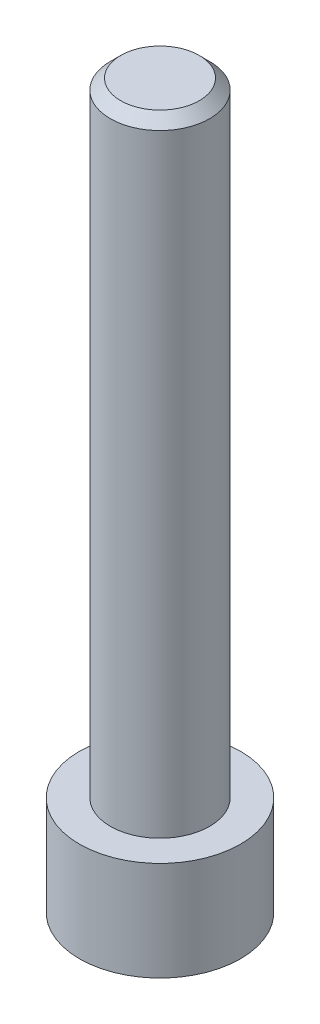
SolidWorks part; units mm, degrees
ref_plane "Front Plane" through (0, 0, 0) normal (0, 0, 1) x (1, 0, 0)
ref_plane "Top Plane" through (0, 0, 0) normal (0, 1, 0) x (1, 0, 0)
ref_plane "Right Plane" through (0, 0, 0) normal (1, 0, 0) x (0, 0, -1)
sketch "Sketch1" plane through (0, 0, 0) normal (0, 1, 0) x (1, 0, 0)
  line L1 (4.4745, 0) -> (2.2372, 3.875) construction
  line L2 (2.2372, 3.875) -> (-2.2372, 3.875) construction
  line L3 (-2.2372, 3.875) -> (-4.4745, 0) construction
  line L4 (-4.4745, 0) -> (-2.2372, -3.875) construction
  line L5 (-2.2372, -3.875) -> (2.2372, -3.875) construction
  line L6 (2.2372, -3.875) -> (4.4745, 0) construction
  circle A0 centre (0, 0) radius 3.875
  dimension "D1" = 7.75
extrude "Boss-Extrude1" add sketch "Sketch1" along normal blind 34.78
sketch "Sketch2" plane through (0, 34.78, 0) normal (0, 1, 0) x (1, 0, 0)
  circle A0 centre (0, 0) radius 2.39
  dimension "D1" = 4.78
extrude "Cut-Extrude1" cut sketch "Sketch2" against normal blind 30 flip side to cut
ref_axis "Axis1" through (0, 4.78, 0) along (0, 1, 0)
chamfer "Chamfer1" distance 0.5 angle 45 1 edges at (0, 34.78, 2.39)
sketch "Sketch5" plane through (0, 34.78, 0) normal (0, 1, 0) x (1, 0, 0)
  circle A0 centre (0, 0) radius 2.39
  dimension "D1" = 4.78
curve "Helix/Spiral1" pitch 0.7 height 25 turns 35.7143
ref_plane "Plane1" through (0, 34.78, 2.39) normal (-0.9989, -0.0466, 0) x (0, 0, 1)
sketch "Sketch8" plane through (0, 0, 0) normal (0, -1, 0) x (1, 0, 0)
  line L1 (2.6443, 0) -> (1.3221, 2.29)
  line L2 (1.3221, 2.29) -> (-1.3221, 2.29)
  line L3 (-1.3221, 2.29) -> (-2.6443, 0)
  line L4 (-2.6443, 0) -> (-1.3221, -2.29)
  line L5 (-1.3221, -2.29) -> (1.3221, -2.29)
  line L6 (1.3221, -2.29) -> (2.6443, 0)
  circle A0 centre (0, 0) radius 2.29 construction
  dimension "D1" = 4.58
extrude "Cut-Extrude2" cut sketch "Sketch8" against normal blind 3.36
